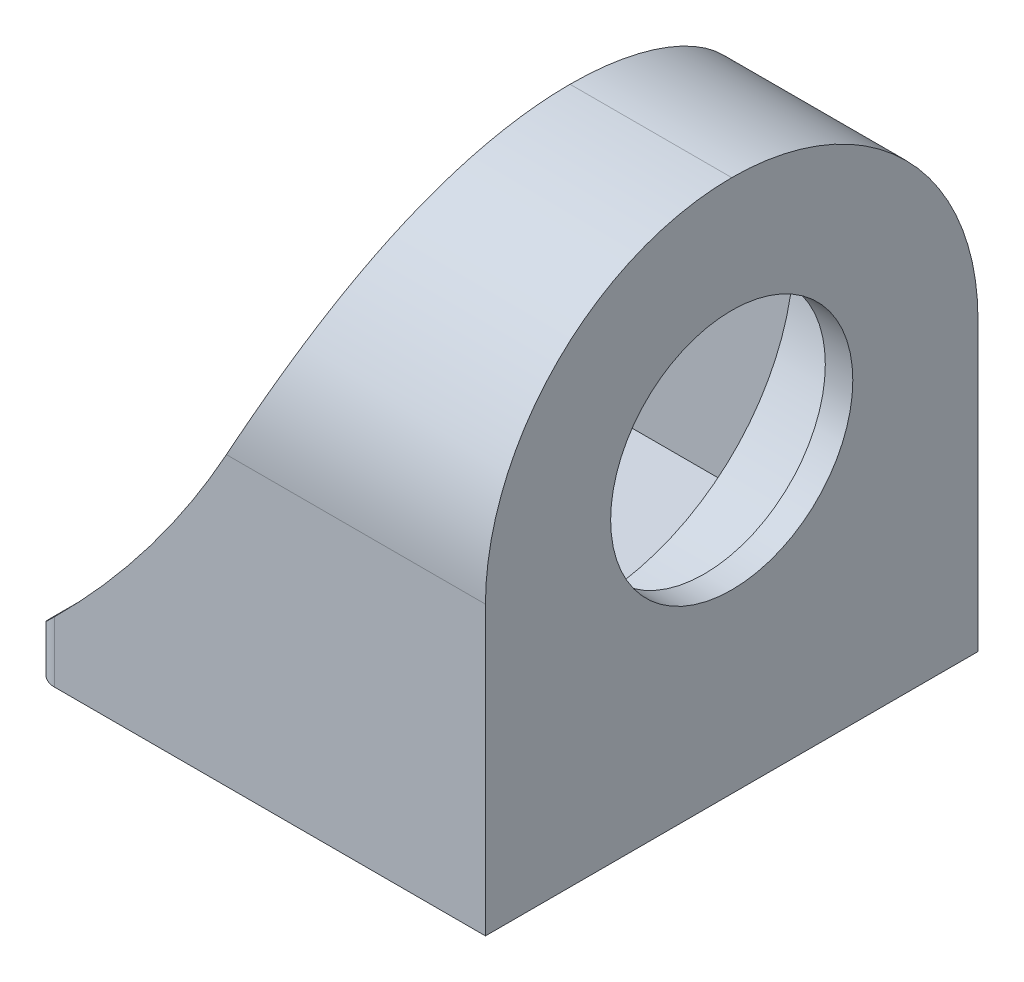
SolidWorks part; units mm, degrees
ref_plane "前视基准面" through (0, 0, 0) normal (0, 0, 1) x (1, 0, 0)
ref_plane "上视基准面" through (0, 0, 0) normal (0, 1, 0) x (1, 0, 0)
ref_plane "右视基准面" through (0, 0, 0) normal (1, 0, 0) x (0, 0, -1)
other "Configuration Table"
sketch "草图1" plane through (0, 0, 0) normal (0, 1, 0) x (1, 0, 0)
  line L1 (-55, -60) -> (55, -60)
  line L2 (-55, -60) -> (-55, 60)
  line L3 (-55, 60) -> (55, 60)
  line L4 (55, -60) -> (55, 60)
  line L5 (-55, -60) -> (55, 60) construction
  line L6 (-55, 60) -> (55, -60) construction
  point P0 (0, 0)
  dimension "D1" = 110
  dimension "D2" = 120
extrude "凸台-拉伸1" add sketch "草图1" along normal blind 130
sketch "草图3" plane through (0, 0, 60) normal (0, 0, 1) x (1, 0, 0)
  line L0 (-55, 0) -> (55, 0) construction
  line L1 (-55, 130) -> (20.6, 130)
  line L2 (-55, 130) -> (-55, 10)
  line L3 (-55, 10) -> (20.6, 10)
  line L4 (20.6, 130) -> (20.6, 10)
  line L5 (55, 130) -> (55, 0) construction
  dimension "D1" = 10
  dimension "D2" = 34.4
extrude "切除-拉伸1" cut sketch "草图3" against normal blind 130
sketch "草图4" plane through (0, 0, 60) normal (0, 0, 1) x (1, 0, 0)
  line L0 (20.6, 130) -> (15.6, 130)
  line L1 (20.6, 10) -> (20.6, 130) construction
  line L2 (-55, 10) -> (20.6, 10) construction
  line L3 (20.6, 10) -> (20.6, 130)
  line L4 (-55, 10) -> (20.6, 10)
  spline S0 degree 2 poles (-55, 10) (-2.665, 59.2488) (15.6, 130) knots 0 0 0 1 1 1
  dimension "D1" = 5
extrude "凸台-拉伸2" add sketch "草图4" against normal blind 5
mirror "镜向1" about plane through (0, 0, 0) normal (0, 0, 1) of "凸台-拉伸2"
sketch "草图5" plane through (0, 0, 55) normal (0, 0, -1) x (-1, 0, 0)
  line L0 (-20.6, 125) -> (-14.2592, 125)
  line L3 (-20.6, 130) -> (-20.6, 10)
  line L4 (-20.6, 10) -> (55, 10)
  line L5 (-15.6, 130) -> (-20.6, 130)
  line L6 (-20.6, 130) -> (-20.6, 10)
  line L7 (-20.6, 10) -> (55, 10)
  line L8 (-15.6, 130) -> (-20.6, 130)
  parabola Q1 (55, 10) -> (-15.6, 130) focus (116.709, 122.3563) apex (15.0863, 58.2197)
  parabola Q2 (55, 10) -> (-15.6, 130) focus (116.709, 122.3563) apex (15.0863, 58.2197)
  line M5 (-20.6, 130) -> (-20.6, 10)
  spline M7 degree 2 poles (-15.6, 130) (2.665, 59.2488) (55, 10) knots 0 0 0 1 1 1
  line M8 (-15.6, 130) -> (-20.6, 130)
  dimension "D2" = 5
  dimension "D1" = 0
extrude "凸台-拉伸3" add sketch "草图5" along normal blind 110 contours L0 M5 M7 M8 region at (17.7558, 127.4013, 55)
fillet "圆角2" radius 55 2 edges at (17.4296, 125, -55)
fillet "圆角3" radius 60 2 edges at (35.3, 130, 60) (35.3, 130, -60)
fillet "圆角4" radius 5 2 edges at (-55, 5, 60) (-55, 5, -60)
sketch "草图6" plane through (20.6, 0, 0) normal (-1, 0, 0) x (0, 0, 1)
  circle A0 centre (0, 72.501) radius 49.5
extrude "切除-拉伸2" cut sketch "草图6" against normal blind 27.7
sketch "草图7" plane through (48.3, 0, 0) normal (-1, 0, 0) x (0, 0, 1)
  circle A0 centre (0, 72.501) radius 29.5
extrude "切除-拉伸5" cut sketch "草图7" against normal through all contours A0
sketch "草图8" plane through (0, 0, 0) normal (0, -1, 0) x (1, 0, 0)
  line L0 (0, 60) -> (0, -60) construction
  line L1 (-50, 60) -> (55, 60) construction
  line L2 (55, -60) -> (-50, -60) construction
  line L3 (55, 0) -> (-55, 0) construction
  line L4 (55, 60) -> (55, -60) construction
  line L5 (-55, -55) -> (-55, 55) construction
  circle A0 centre (0, 0) radius 2.5
  circle A1 centre (0, 17.25) radius 2
  circle A2 centre (0, -17.25) radius 2
  dimension "D1" = 4
  dimension "D2" = 34.5
extrude "切除-拉伸6" cut sketch "草图8" against normal blind 10
